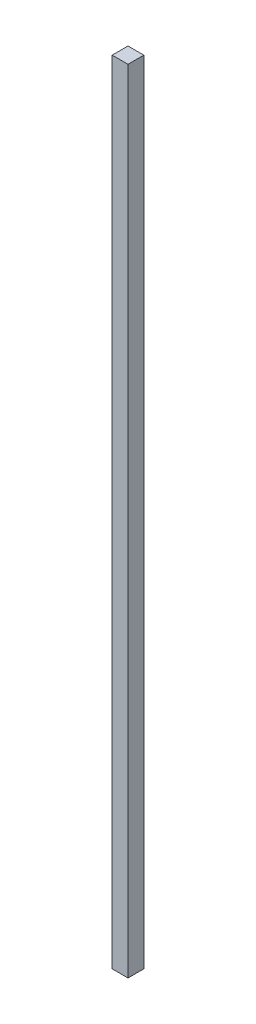
SolidWorks part; units mm, degrees
ref_plane "Ebene vorne" through (0, 0, 0) normal (0, 0, 1) x (1, 0, 0)
ref_plane "Ebene oben" through (0, 0, 0) normal (0, 1, 0) x (1, 0, 0)
ref_plane "Ebene rechts" through (0, 0, 0) normal (1, 0, 0) x (0, 0, -1)
sketch "Skizze1" plane through (0, 0, 0) normal (0, 1, 0) x (1, 0, 0)
  line L1 (0, 0) -> (50, 0)
  line L2 (0, 0) -> (0, 50)
  line L3 (0, 50) -> (50, 50)
  line L4 (50, 0) -> (50, 50)
  dimension "D1" = 50
  dimension "D2" = 50
extrude "Aufsatz-Linear austragen1" add sketch "Skizze1" along normal blind 2500
